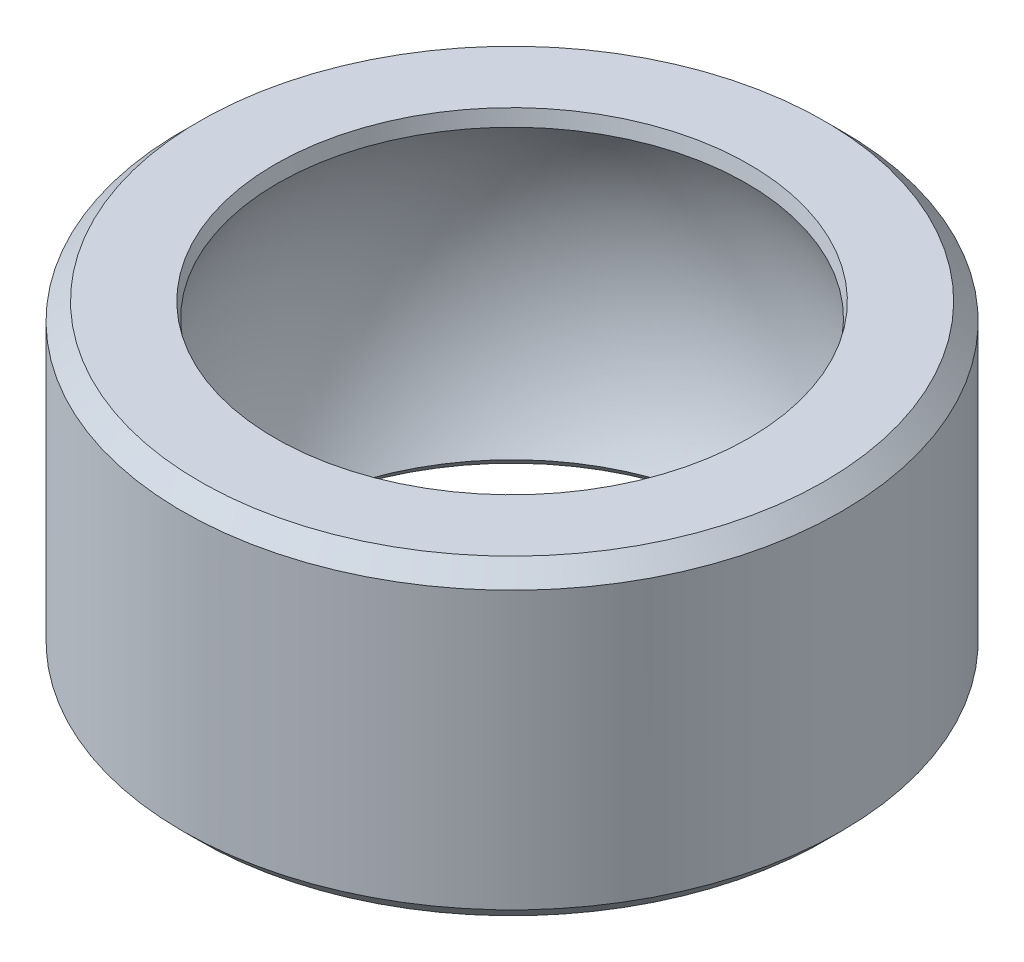
SolidWorks part; units mm, degrees
ref_plane "Front Plane" through (0, 0, 0) normal (0, 0, 1) x (1, 0, 0)
ref_plane "Top Plane" through (0, 0, 0) normal (0, 1, 0) x (1, 0, 0)
ref_plane "Right Plane" through (0, 0, 0) normal (1, 0, 0) x (0, 0, -1)
sketch "Sketch2" plane through (0, 0, 0) normal (0, 0, 1) x (1, 0, 0)
  line L0 (0, -4.5) -> (0, 4.5) construction
  line L1 (0, 0) -> (-7.9, 0) construction
  line L2 (0, 4.5) -> (-6.4931, 4.5) construction
  line L3 (0, 0) -> (-9.525, 0) construction
  line L4 (-9.525, -4.5) -> (-9.525, 4.5)
  line L5 (-6.4931, 4.5) -> (-9.525, 4.5)
  line L6 (-6.4931, -4.5) -> (-9.525, -4.5)
  arc A0 (-6.4931, -4.5) -> (-6.4931, 4.5) centre (0, 0) cw
  point P4 (0, 0)
  point P13 (-9.525, 0)
  dimension "D1" = 7.9
  dimension "D2" = 9
  dimension "D3" = 9.525
revolve "Revolve1" add sketch "Sketch2" angle 360 about L0
chamfer "Chamfer1" distance 0.5 angle 45 4 edges at (6.4931, -4.5, 0) (9.525, -4.5, 0) (9.525, 4.5, 0) (6.4931, 4.5, 0) first distance on face at (6.4931, -4.5, 0) first distance on face at (9.525, -4.5, 0) first distance on face at (9.525, 4.5, 0) first distance on face at (6.4931, 4.5, 0)
